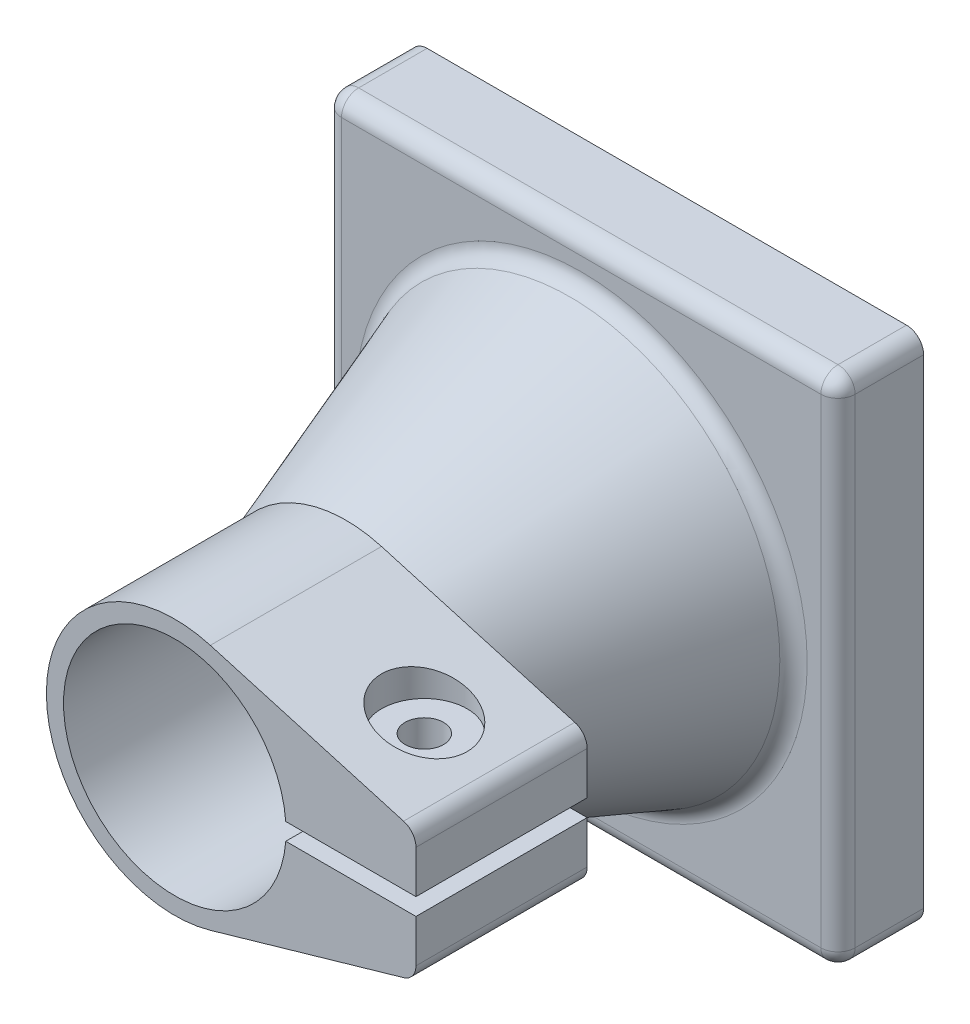
SolidWorks part; units mm, degrees
ref_plane "Ön Düzlem" through (0, 0, 0) normal (0, 0, 1) x (1, 0, 0)
ref_plane "Üst Düzlem" through (0, 0, 0) normal (0, 1, 0) x (1, 0, 0)
ref_plane "Sağ Düzlem" through (0, 0, 0) normal (1, 0, 0) x (0, 0, -1)
sketch "Sketch1" plane through (0, 0, 0) normal (0, 0, 1) x (1, 0, 0)
  line L1 (-30, 30) -> (30, 30)
  line L2 (-30, 30) -> (-30, -30)
  line L3 (-30, -30) -> (30, -30)
  line L4 (30, 30) -> (30, -30)
  dimension "D1" = 60
  dimension "D2" = 60
  dimension "D3" = 30
  dimension "D4" = 30
extrude "Boss-Extrude1" add sketch "Sketch1" along normal blind 10
sketch "Sketch2" plane through (0, 0, 0) normal (0, 1, 0) x (1, 0, 0)
  line L0 (-25, -10) -> (-15, -37.4748)
  line L1 (-30, -10) -> (30, -10) construction
  line L2 (0, -38.641) -> (0, 14.1274) construction
  line L3 (-25, -10) -> (0, -10)
  line L4 (-15, -37.4748) -> (0, -37.4748)
  line L5 (0, -10) -> (0, -37.4748)
  dimension "D1" = 70
  dimension "D2" = 15
  dimension "D3" = 5
revolve "Revolve1" add sketch "Sketch2" angle 360 about L2
fillet "Fillet1" radius 2 5 edges at (25, 0, 10) (0, 30, 10) (30, 0, 10) (0, -30, 10) (-30, 0, 10)
fillet "Fillet2" radius 2 8 edges at (29.4142, -29.4142, 9.4142) (-29.4142, -29.4142, 9.4142) (29.4142, 29.4142, 9.4142) (-29.4142, 29.4142, 9.4142) (30, -30, 4) (-30, -30, 4) (30, 30, 4) (-30, 30, 4)
sketch "Sketch3" plane through (0, 0, 37.4748) normal (0, 0, 1) x (1, 0, 0)
  circle A0 centre (0, 0) radius 13
  circle A1 centre (0, 0) radius 15
  dimension "D1" = 26
  dimension "D2" = 30
extrude "Boss-Extrude2" add sketch "Sketch3" along normal blind 20
sketch "Sketch4" plane through (0, 0, 37.4748) normal (0, 0, 1) x (1, 0, 0)
  circle A1 centre (0, 0) radius 13
  dimension "D1" = 26
extrude "Cut-Extrude1" cut sketch "Sketch4" against normal blind 20
sketch "Sketch7" plane through (0, 0, 57.4748) normal (0, 0, 1) x (1, 0, 0)
  line L0 (4.1489, 14.4148) -> (28.1736, 7.5)
  line L1 (-8.4406, 0) -> (36.3969, 0) construction
  line L2 (4.1489, -14.4148) -> (28.1736, -7.5)
  line L3 (28.1736, 7.5) -> (28.1736, -7.5)
  circle A0 centre (0, 0) radius 15 construction
  arc A1 (4.1489, 14.4148) -> (4.1489, -14.4148) centre (0, 0) cw
  dimension "D1" = 25
  dimension "D2" = 15
extrude "Boss-Extrude4" add sketch "Sketch7" against normal blind 20
fillet "Fillet5" radius 2 2 edges at (28.1736, 7.5, 47.4748) (28.1736, -7.5, 47.4748)
ref_plane "Plane1" through (0, 20, 0) normal (0, 1, 0) x (1, 0, 0)
sketch "Sketch12" plane through (0, 20, 0) normal (0, 1, 0) x (1, 0, 0)
  line L0 (-19.711, -47.4748) -> (47.4674, -47.4748) construction
  line L1 (4.1489, -37.4748) -> (-15, -37.4748) construction
  line L2 (4.1489, -37.4748) -> (4.1489, -57.4748) construction
  circle A0 centre (19.1489, -47.4748) radius 2.25
  dimension "D1" = 4.5
  dimension "10" = 10
  dimension "15" = 15
extrude "Cut-Extrude2" cut sketch "Sketch12" against normal up to surface (30.0975 mm away) up to face at (15.4378, -11.1656, 47.4748)
sketch "Sketch13" plane through (0, 20, 0) normal (0, 1, 0) x (1, 0, 0)
  circle A0 centre (19.1489, -47.4748) radius 5
  dimension "D1" = 10
extrude "Cut-Extrude3" cut sketch "Sketch13" against normal blind 12
ref_plane "Plane2" through (0, -20, 0) normal (0, 1, 0) x (1, 0, 0)
sketch "Sketch14" plane through (0, -20, 0) normal (0, 1, 0) x (1, 0, 0)
  circle A0 centre (19.1489, -47.4748) radius 5
  dimension "10" = 10
extrude "Cut-Extrude4" cut sketch "Sketch14" along normal blind 12
ref_plane "Plane3" through (0, 0, 57.4748) normal (0, 0, 1) x (1, 0, 0)
sketch "Sketch15" plane through (0, 0, 57.4748) normal (0, 0, 1) x (1, 0, 0)
  line L0 (28.1736, 1) -> (12.9615, 1)
  line L1 (28.1736, -5.9944) -> (28.1736, 5.9944) construction
  line L2 (-5.2184, 0) -> (55.0529, 0) construction
  line L3 (28.1736, -1) -> (12.9615, -1)
  line L4 (28.1736, 1) -> (28.1736, -1)
  circle A0 centre (0, 0) radius 13 construction
  arc A1 (12.9615, 1) -> (12.9615, -1) centre (0, 0) cw
  dimension "3" = 2
extrude "Cut-Extrude12" cut sketch "Sketch15" against normal up to surface (20 mm away) up to face at (21.5987, 0, 37.4748)
